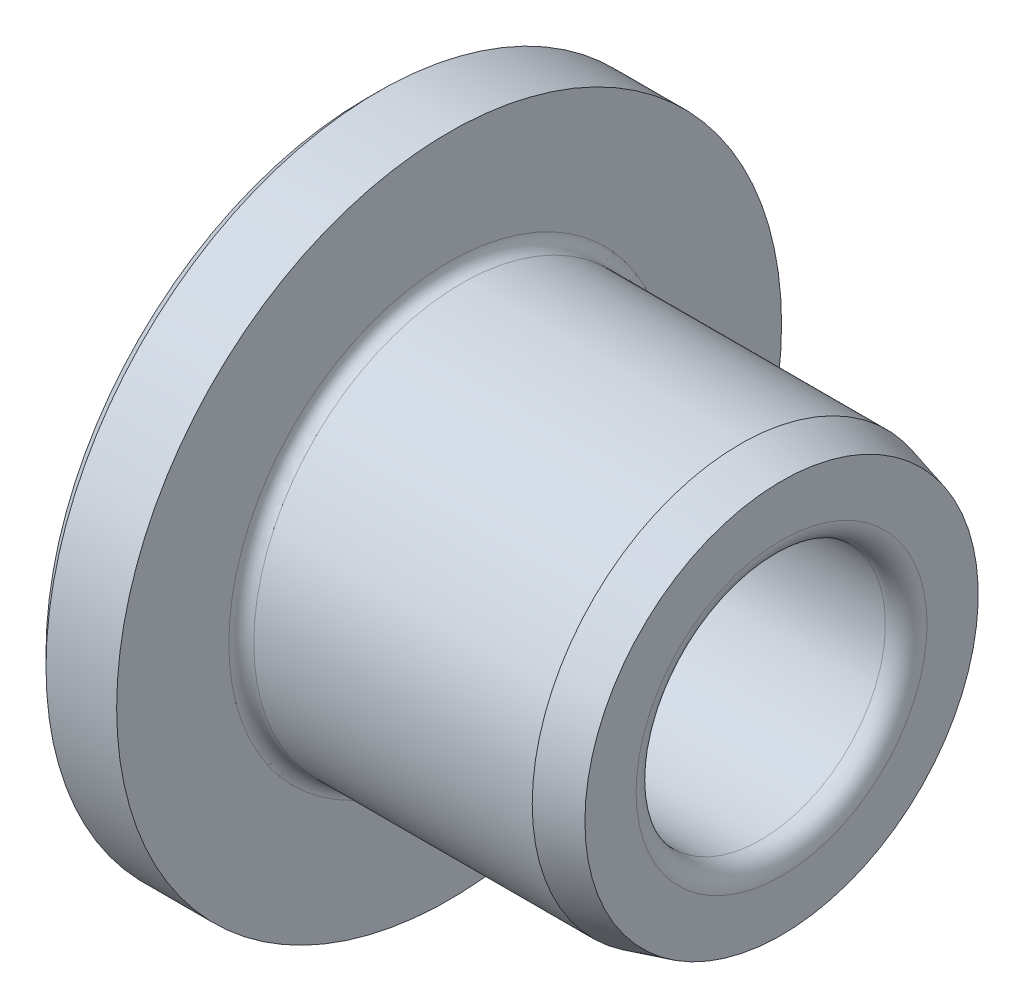
SolidWorks part; units mm, degrees
ref_plane "Front Plane" through (0, 0, 0) normal (0, 0, 1) x (1, 0, 0)
ref_plane "Top Plane" through (0, 0, 0) normal (0, 1, 0) x (1, 0, 0)
ref_plane "Right Plane" through (0, 0, 0) normal (1, 0, 0) x (0, 0, -1)
sketch "Sketch1" plane through (0, 0, 0) normal (0, 0, 1) x (1, 0, 0)
  line L0 (-2, 0) -> (8, 0) construction
  line L1 (-2, 3) -> (8, 3)
  line L2 (8, 3) -> (8, 5)
  line L3 (8, 5) -> (0, 5)
  line L4 (0, 5) -> (0, 8)
  line L5 (0, 8) -> (-2, 8)
  line L6 (-2, 8) -> (-2, 3)
  dimension "D_s" = 6
  dimension "H" = 16
  dimension "L" = 10
  dimension "D" = 10
  dimension "T_s" = 2
revolve "Revolve1" add sketch "Sketch1" angle 360 about L0
chamfer "Chamfer1" distance 0.3 angle 45 1 edges at (-2, 0, 8)
fillet "Fillet1" radius 0.3 1 edges at (0, 0, 5)
chamfer "Chamfer2" [suppressed] distance 3 angle 10
chamfer "Chamfer3" distance 1 angle 15 1 edges at (8, 0, 5) first distance on face at (0.3, 0, 5)
chamfer "Chamfer4" [suppressed] distance 1 angle 10
fillet "Fillet2" [suppressed] radius 1
fillet "Fillet3" [suppressed] radius 0.5
fillet "Fillet4" [suppressed] radius 0.3
fillet "Fillet5" radius 0.5 2 edges at (8, 0, 3) (-2, 0, 3)
